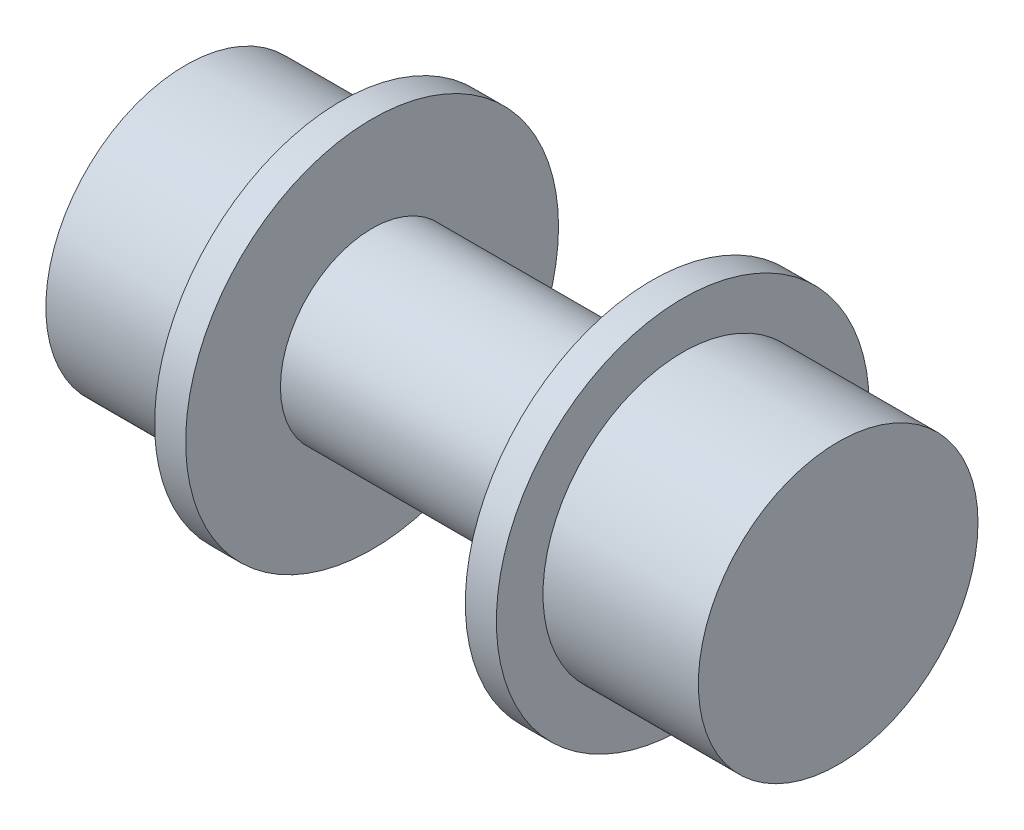
SolidWorks part; units mm, degrees
ref_plane "Front Plane" through (0, 0, 0) normal (0, 0, 1) x (1, 0, 0)
ref_plane "Top Plane" through (0, 0, 0) normal (0, 1, 0) x (1, 0, 0)
ref_plane "Right Plane" through (0, 0, 0) normal (1, 0, 0) x (0, 0, -1)
sketch "Sketch1" plane through (0, 0, 0) normal (1, 0, 0) x (0, 0, -1)
  circle A0 centre (0, 0) radius 37.465
  circle A1 centre (0, 0) radius 57.15
  circle A2 centre (0, 0) radius 76.2
  dimension "D1" = 74.93
  dimension "D2" = 114.3
  dimension "D3" = 19.05
extrude "Boss-Extrude1" add sketch "Sketch1" along normal mid plane 114.3 contours A0 region at (0, 0, 0)
extrude "Boss-Extrude2" add sketch "Sketch1<3>" along normal blind 12.7 from surface contours A0 | A1 A0 | A2 A1 region at (0, 0, 0) region at (0, 0, 55.5336) region at (0, 0, 74.0447) starting at face at (57.15, 0, -37.465)
sketch "Sketch1<3>" plane through (0, 0, 0) normal (1, 0, 0) x (0, 0, -1) same geometry as "Sketch1"
extrude "Boss-Extrude3" add sketch "Sketch1<4>" along normal blind 63.5 from surface contours A1 A0 | A0 region at (0, 0, 0) region at (0, 0, 55.5336) starting at face at (69.85, 0, -76.2)
sketch "Sketch1<4>" plane through (0, 0, 0) normal (1, 0, 0) x (0, 0, -1) same geometry as "Sketch1"
extrude "Boss-Extrude4" add sketch "Sketch1<5>" against normal blind 12.7 from surface contours A0 | A1 A0 | A2 A1 region at (0, 0, 0) region at (0, 0, 55.5336) region at (0, 0, 74.0447) starting at face at (-57.15, 0, -37.465)
sketch "Sketch1<5>" plane through (0, 0, 0) normal (1, 0, 0) x (0, 0, -1) same geometry as "Sketch1"
extrude "Boss-Extrude5" add sketch "Sketch1<6>" against normal blind 63.5 from surface contours A0 | A1 A0 region at (0, 0, 0) region at (0, 0, 55.5336) starting at face at (-69.85, 0, -76.2)
sketch "Sketch1<6>" plane through (0, 0, 0) normal (1, 0, 0) x (0, 0, -1) same geometry as "Sketch1"
